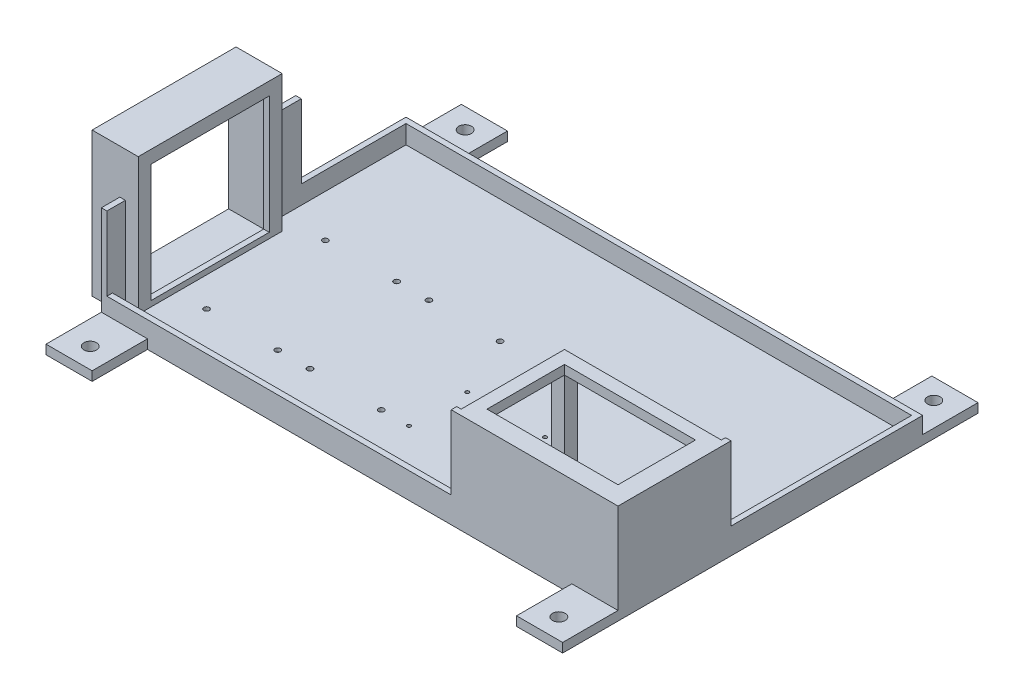
SolidWorks part; units mm, degrees
ref_plane "Front Plane" through (0, 0, 0) normal (0, 0, 1) x (1, 0, 0)
ref_plane "Top Plane" through (0, 0, 0) normal (0, 1, 0) x (1, 0, 0)
ref_plane "Right Plane" through (0, 0, 0) normal (1, 0, 0) x (0, 0, -1)
sketch "Sketch1" plane through (0, 0, 0) normal (0, 1, 0) x (1, 0, 0)
  line L1 (-140, -82.55) -> (140, -82.55)
  line L2 (-140, -82.55) -> (-140, 82.55)
  line L3 (-140, 82.55) -> (140, 82.55)
  line L4 (140, -82.55) -> (140, 82.55)
  line L5 (-140, -82.55) -> (140, 82.55) construction
  line L6 (-140, 82.55) -> (140, -82.55) construction
  point P0 (0, 0)
  dimension "D1" = 165.1
  dimension "D2" = 280
extrude "Floor" add sketch "Sketch1" along normal blind 4
sketch "Sketch2" plane through (0, 4, 0) normal (0, 1, 0) x (1, 0, 0)
  line L0 (137, -79.55) -> (137, 79.55)
  line L1 (137, 79.55) -> (-137, 79.55)
  line L2 (-137, 79.55) -> (-137, -79.55)
  line L3 (-137, -79.55) -> (137, -79.55)
  line L4 (140, -82.55) -> (140, 82.55)
  line L5 (140, 82.55) -> (-140, 82.55)
  line L6 (-140, 82.55) -> (-140, -82.55)
  line L7 (-140, -82.55) -> (140, -82.55)
  line L8 (140, -82.55) -> (140, 82.55)
  line L9 (140, 82.55) -> (-140, 82.55)
  line L10 (-140, 82.55) -> (-140, -82.55)
  line L11 (-140, -82.55) -> (140, -82.55)
  dimension "D1" = 0
  dimension "D2" = 3
extrude "Wall" add sketch "Sketch2" along normal blind 10
sketch "Sketch4" plane through (0, 4, 0) normal (0, 1, 0) x (1, 0, 0)
  line L0 (130, -30.55) -> (59, -30.55)
  line L1 (137, -79.55) -> (52, -79.55)
  line L2 (137, -79.55) -> (137, -23.55)
  line L3 (137, -23.55) -> (52, -23.55)
  line L4 (52, -79.55) -> (52, -23.55)
  line L5 (59, -72.55) -> (59, -30.55)
  line L6 (130, -72.55) -> (59, -72.55)
  line L7 (130, -72.55) -> (130, -30.55)
  dimension "D1" = 85
  dimension "D2" = 56
  dimension "D3" = 7
extrude "Rpi stand" add sketch "Sketch4" along normal blind 5 from offset 45
sketch "Sketch7" plane through (0, 14, 0) normal (0, 1, 0) x (1, 0, 0)
  line L0 (-137, 79.55) -> (-137, -79.55) construction
  line L1 (-140, -82.55) -> (-137, -82.55)
  line L2 (-140, -82.55) -> (-140, 22.7839)
  line L3 (-140, 22.7839) -> (-137, 22.7839)
  line L4 (-137, -82.55) -> (-137, 22.7839)
  line L5 (-137, -79.55) -> (137, -79.55) construction
  line L6 (140, -82.55) -> (49.6123, -82.55)
  line L7 (140, -82.55) -> (140, -79.55)
  line L8 (137, -79.55) -> (49.6123, -79.55)
  line L9 (49.6123, -82.55) -> (49.6123, -79.55)
  line L10 (137, -79.55) -> (137, 79.55) construction
  line L12 (140, -79.55) -> (140, -21.3069)
  line L13 (140, -21.3069) -> (137, -21.3069)
  line L14 (137, -79.55) -> (137, -21.3069)
  line L15 (-137, -79.55) -> (137, -79.55) construction
extrude "Temp support" add sketch "Sketch7" along normal blind 40
sketch "Sketch3" plane through (0, 0, 0) normal (0, 1, 0) x (1, 0, 0)
  line L0 (-127, 101.6) -> (127, 101.6) construction
  line L1 (-140, 82.55) -> (-115, 82.55)
  line L2 (-140, 82.55) -> (-140, 112.55)
  line L3 (-140, 112.55) -> (-115, 112.55)
  line L4 (-115, 82.55) -> (-115, 112.55)
  line L5 (140, 82.55) -> (115, 82.55)
  line L6 (140, 82.55) -> (140, 112.55)
  line L7 (140, 112.55) -> (115, 112.55)
  line L8 (115, 82.55) -> (115, 112.55)
  line L9 (-140, -82.55) -> (-115, -82.55)
  line L10 (-140, -82.55) -> (-140, -112.55)
  line L11 (-140, -112.55) -> (-115, -112.55)
  line L12 (-115, -82.55) -> (-115, -112.55)
  line L13 (140, -82.55) -> (115, -82.55)
  line L14 (140, -82.55) -> (140, -112.55)
  line L15 (140, -112.55) -> (115, -112.55)
  line L16 (115, -82.55) -> (115, -112.55)
  line L17 (127, 101.6) -> (127, -101.6) construction
  line L18 (127, -101.6) -> (-127, -101.6) construction
  line L19 (-127, -101.6) -> (-127, 101.6) construction
  line L20 (-140, 30.6215) -> (140, 30.6215) construction
  line L22 (140, -21.3069) -> (140, 82.55) construction
  line L23 (0, 101.6) -> (0, -101.6) construction
  line L24 (-140, 22.7839) -> (-140, -82.55) construction
  line L25 (140, -21.3069) -> (140, 82.55) construction
  line L26 (-137, -82.55) -> (49.6123, -82.55) construction
  circle A0 centre (-127, 101.6) radius 3.429
  circle A1 centre (127, 101.6) radius 3.429
  circle A2 centre (127, -101.6) radius 3.429
  circle A3 centre (-127, -101.6) radius 3.429
  point P28 (-127.5, -82.55)
  point P29 (-115, -97.55)
  point P30 (127.5, -82.55)
  point P31 (-115, 97.55)
  dimension "D5" = 6.858
  dimension "D1" = 25
  dimension "D2" = 25
  dimension "D3" = 30
  dimension "D4" = 30
  dimension "D6" = 203.2
  dimension "D7" = 254
extrude "Brackets" add sketch "Sketch3" along normal blind 5
sketch "Sketch5" plane through (-140, 0, 0) normal (-1, 0, 0) x (0, 0, 1)
  line L0 (-5.45, 78) -> (72.55, 78)
  line L1 (-1.45, 4) -> (68.55, 4)
  line L2 (-1.45, 4) -> (-1.45, 74)
  line L3 (-1.45, 74) -> (68.55, 74)
  line L4 (68.55, 4) -> (68.55, 74)
  line L5 (72.55, 0) -> (72.55, 78)
  line L6 (-5.45, 0) -> (72.55, 0)
  line L7 (-5.45, 0) -> (-5.45, 78)
  line L9 (112.55, 5) -> (112.55, 0) construction
  line L11 (-79.55, 4) -> (79.55, 4) construction
  dimension "D1" = 70
  dimension "D2" = 70
  dimension "D5" = 40
  dimension "D3" = 4
extrude "Fan Holder" add sketch "Sketch5" along normal blind 15 and the other way blind 10
sketch "Sketch8" plane through (-140, 0, 0) normal (-1, 0, 0) x (0, 0, 1)
  line L4 (-1.45, 54) -> (-1.45, 4)
  line L5 (-1.45, 4) -> (68.55, 4)
  line L6 (68.55, 4) -> (68.55, 54)
  line L7 (68.55, 54) -> (-1.45, 54)
  line L8 (-1.45, 54) -> (-1.45, 4)
  line L9 (-1.45, 4) -> (68.55, 4)
  line L10 (68.55, 4) -> (68.55, 54)
  line L15 (68.55, 54) -> (-1.45, 54)
  dimension "D1" = 0
extrude "Fan hole" cut sketch "Sketch8" against normal up to next (3 mm away)
sketch "Sketch11" plane through (-130, 0, 0) normal (-1, 0, 0) x (0, 0, 1)
  line L4 (-5.45, 78) -> (-5.45, 0)
  line L5 (-5.45, 0) -> (72.55, 0)
  line L6 (72.55, 0) -> (72.55, 78)
  line L7 (72.55, 78) -> (-5.45, 78)
  line L8 (-5.45, 78) -> (-5.45, 0)
  line L9 (-5.45, 0) -> (72.55, 0)
  line L10 (72.55, 0) -> (72.55, 78)
  line L11 (72.55, 78) -> (-5.45, 78)
  line L16 (1.55, 71) -> (1.55, 7)
  line L17 (1.55, 7) -> (65.55, 7)
  line L18 (65.55, 7) -> (65.55, 71)
  line L19 (65.55, 71) -> (1.55, 71)
  line L20 (1.55, 71) -> (1.55, 7)
  line L21 (1.55, 7) -> (65.55, 7)
  line L22 (65.55, 7) -> (65.55, 71)
  line L23 (65.55, 71) -> (1.55, 71)
  dimension "D1" = 0
  dimension "D2" = 7
extrude "Boss-Extrude9" add sketch "Sketch11" along normal blind 3
sketch "Sketch12" plane through (0, 49, 0) normal (0, -1, 0) x (1, 0, 0)
  line L1 (52, 23.55) -> (59, 23.55)
  line L2 (52, 23.55) -> (52, 30.55)
  line L3 (52, 30.55) -> (59, 30.55)
  line L4 (59, 23.55) -> (59, 30.55)
  dimension "D1" = 7
  dimension "D2" = 7
extrude "Boss-Extrude10" add sketch "Sketch12" along normal up to next
sketch "Sketch13" plane through (0, 4, 0) normal (0, 1, 0) x (1, 0, 0)
  line L0 (-137, -79.55) -> (137, -79.55) construction
  line L1 (-137, -82.55) -> (-137, -72.55) construction
  line L2 (-114, -51.55) -> (-114, 12.85) construction
  line L3 (-114, 12.85) -> (-75.4, 12.85) construction
  line L4 (-114, -51.55) -> (-75.4, -51.55) construction
  line L5 (-75.4, 12.85) -> (-75.4, -51.55) construction
  line L6 (-75.4, 12.85) -> (-57.9, 12.85) construction
  line L7 (-57.9, 12.85) -> (-57.9, -51.55) construction
  line L8 (-57.9, -51.55) -> (-19.3, -51.55) construction
  line L9 (-19.3, -51.55) -> (-19.3, 12.85) construction
  line L10 (-19.3, 12.85) -> (-57.9, 12.85) construction
  line L11 (-75.4, -51.55) -> (-57.9, -51.55) construction
  line L12 (-19.3, -51.55) -> (-4.3, -51.55) construction
  line L13 (-4.3, -51.55) -> (-4.3, -19.95) construction
  line L14 (-4.3, -19.95) -> (37.87, -19.95) construction
  line L15 (37.87, -19.95) -> (37.87, -51.55) construction
  line L16 (37.87, -51.55) -> (-4.3, -51.55) construction
  circle A0 centre (-114, -51.55) radius 1.5
  circle A1 centre (-114, 12.85) radius 1.5
  circle A2 centre (-75.4, 12.85) radius 1.5
  circle A3 centre (-75.4, -51.55) radius 1.5
  circle A4 centre (-57.9, 12.85) radius 1.5
  circle A5 centre (-57.9, -51.55) radius 1.5
  circle A6 centre (-19.3, -51.55) radius 1.5
  circle A7 centre (-19.3, 12.85) radius 1.5
  circle A8 centre (-4.3, -51.55) radius 1
  circle A9 centre (-4.3, -19.95) radius 1
  circle A10 centre (37.87, -19.95) radius 1
  circle A11 centre (37.87, -51.55) radius 1
  point P6 (-137, -77.55)
  dimension "D1" = 28
  dimension "D2" = 23
  dimension "D3" = 3
  dimension "D6" = 3
  dimension "D7" = 3
  dimension "D8" = 3
  dimension "D11" = 3
  dimension "D12" = 3
  dimension "D13" = 3
  dimension "D14" = 3
  dimension "D16" = 2
  dimension "D18" = 2
  dimension "D20" = 2
  dimension "D21" = 2
  dimension "D4" = 64.4
  dimension "D5" = 38.6
  dimension "D9" = 17.5
  dimension "D10" = 38.6
  dimension "D15" = 15
  dimension "D17" = 31.6
  dimension "D19" = 42.17
extrude "Cut-Extrude1" cut sketch "Sketch13" against normal blind 2
equation "\"D2@Sketch3\"=\"D1@Sketch3\""
equation "\"D4@Sketch3\"=\"D3@Sketch3\""
